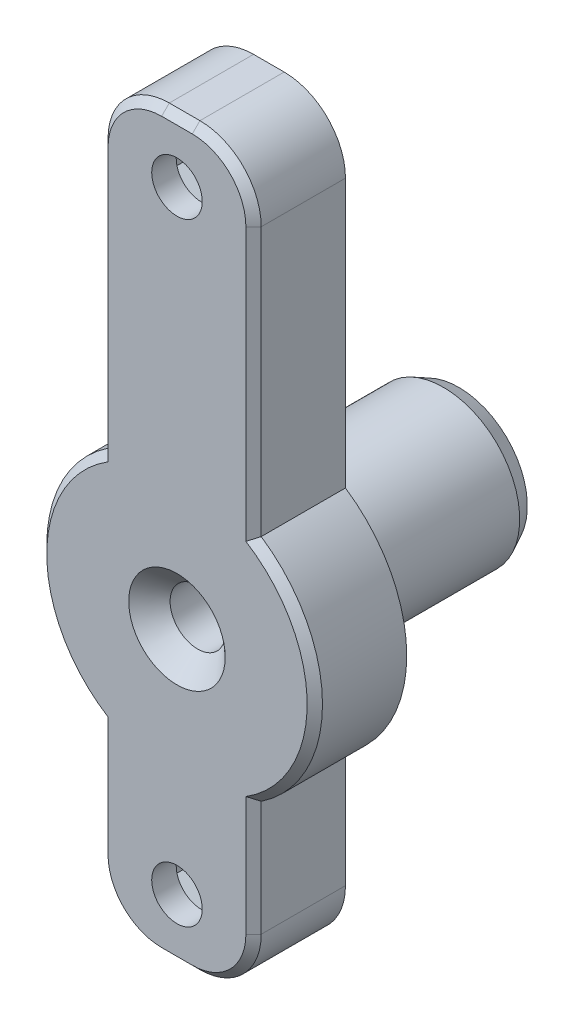
SolidWorks part; units mm, degrees
note: The reader was unsure of these and kept them because the rebuilt part matched: shared geometry of "Sketch1<5>".
material "ABS"
ref_plane "Front Plane" through (0, 0, 0) normal (0, 0, 1) x (1, 0, 0)
ref_plane "Top Plane" through (0, 0, 0) normal (0, 1, 0) x (1, 0, 0)
ref_plane "Right Plane" through (0, 0, 0) normal (1, 0, 0) x (0, 0, -1)
sketch "Sketch1" plane through (0, 0, 0) normal (0, 0, 1) x (1, 0, 0)
  line L0 (-5, 25) -> (-5, 7.4833)
  line L1 (5, 25) -> (5, 7.4833)
  line L2 (-4, 0) -> (-7, 0) construction
  line L3 (-3.9799, 0.4) -> (-6.9886, 0.4)
  line L4 (-3.9799, -0.4) -> (-6.9886, -0.4)
  line L5 (-1.6436, 3.6467) -> (-3.1479, 6.2523)
  line L6 (-4, 0.4) -> (-7, 0.4) construction
  line L7 (-4, -0.4) -> (-7, -0.4) construction
  line L12 (-2.3364, 3.2467) -> (-3.8407, 5.8523)
  line L13 (-2, 3.4641) -> (-3.5, 6.0622) construction
  line L14 (2.3364, 3.2467) -> (3.8407, 5.8523)
  line L15 (1.6436, 3.6467) -> (3.1479, 6.2523)
  line L16 (2, 3.4641) -> (3.5, 6.0622) construction
  line L17 (1, 25) -> (-1, 25) construction
  line L20 (1, 21) -> (-1, 21)
  line L21 (1, 29) -> (-1, 29)
  line L22 (-5, -15) -> (-5, -7.4833)
  line L23 (5, -15) -> (5, -7.4833)
  line L24 (1, -15) -> (-1, -15) construction
  line L25 (1, -19) -> (-1, -19)
  line L26 (1, -11) -> (-1, -11)
  line L27 (-6.5886, 0.4) -> (-7, 0)
  line L28 (-2.9479, 5.9059) -> (-3.5, 6.0622)
  line L29 (3.6407, 5.5059) -> (3.5, 6.0622)
  line L30 (3.9799, -0.4) -> (6.9886, -0.4)
  line L31 (3.9799, 0.4) -> (6.9886, 0.4)
  line L32 (4, 0) -> (7, 0) construction
  line L33 (6.5886, -0.4) -> (7, 0)
  line L34 (1.6436, -3.6467) -> (3.1479, -6.2523)
  line L35 (2.3364, -3.2467) -> (3.8407, -5.8523)
  line L36 (2, -3.4641) -> (3.5, -6.0622) construction
  line L37 (2.9479, -5.9059) -> (3.5, -6.0622)
  line L38 (-2.3364, -3.2467) -> (-3.8407, -5.8523)
  line L39 (-1.6436, -3.6467) -> (-3.1479, -6.2523)
  line L40 (-2, -3.4641) -> (-3.5, -6.0622) construction
  line L41 (-3.6407, -5.5059) -> (-3.5, -6.0622)
  circle A2 centre (0, 0) radius 9
  circle A3 centre (0, 0) radius 7
  circle A4 centre (0, 25) radius 1.65
  circle A5 centre (0, 25) radius 5
  circle A6 centre (0, 0) radius 3.1
  circle A7 centre (0, 0) radius 4
  circle A16 centre (0, 0) radius 1.75
  circle A17 centre (0, 13) radius 1.35 construction
  circle A18 centre (0, -15) radius 1.65
  circle A19 centre (0, -15) radius 5
  arc A20 (1, 21) -> (1, 29) centre (1, 25) ccw
  arc A21 (-1, 29) -> (-1, 21) centre (-1, 25) ccw
  arc A22 (1, -19) -> (1, -11) centre (1, -15) ccw
  arc A23 (-1, -11) -> (-1, -19) centre (-1, -15) ccw
  point P39 (0, 25)
  point P53 (0, -15)
  point P67 (0, 0)
  dimension "D1" = 6.2
  dimension "D2" = 8
  dimension "D3" = 18
  dimension "D4" = 14
  dimension "D5" = 3.3
  dimension "D7" = 10
  dimension "D8" = 0.4
  dimension "D11" = 3.5
  dimension "D12" = 2.7
  dimension "D15" = 3.3
  dimension "D16" = 10
  dimension "D6" = 25
  dimension "D9" = 0.4
  dimension "D10" = 6
  dimension "D13" = 12
  dimension "D14" = 15
  dimension "D17" = 8
  dimension "D18" = 2
  dimension "D19" = 8
  dimension "D20" = 2
  dimension "D21" = 0.4
extrude "Boss-Extrude1" add sketch "Sketch1" along normal blind 6
sketch "Sketch2" plane through (0, 0, 0) normal (0, 0, -1) x (-1, 0, 0)
  line L0 (-0.2571, -2.8886) -> (0, -2.5822)
  line L1 (0, -2.5822) -> (0.2571, -2.8886)
  line L2 (-0.2571, -2.8886) -> (0.2571, -2.8886) construction
  line L3 (-0.9674, -2.7339) -> (-0.6422, -2.501)
  line L4 (-0.6422, -2.501) -> (-0.4693, -2.8618)
  line L5 (-0.9674, -2.7339) -> (-0.4693, -2.8618) construction
  line L6 (-1.6169, -2.4074) -> (-1.244, -2.2628)
  line L7 (-1.244, -2.2628) -> (-1.1663, -2.6551)
  line L8 (-1.6169, -2.4074) -> (-1.1663, -2.6551) construction
  line L9 (-2.1648, -1.9297) -> (-1.7676, -1.8823)
  line L10 (-1.7676, -1.8823) -> (-1.7899, -2.2817)
  line L11 (-2.1648, -1.9297) -> (-1.7899, -2.2817) construction
  line L12 (-2.5767, -1.3307) -> (-2.1802, -1.3836)
  line L13 (-2.1802, -1.3836) -> (-2.3011, -1.7649)
  line L14 (-2.5767, -1.3307) -> (-2.3011, -1.7649) construction
  line L15 (-2.8267, -0.6481) -> (-2.4558, -0.7979)
  line L16 (-2.4558, -0.7979) -> (-2.6677, -1.1372)
  line L17 (-2.8267, -0.6481) -> (-2.6677, -1.1372) construction
  line L18 (-2.899, 0.0752) -> (-2.5771, -0.1621)
  line L19 (-2.5771, -0.1621) -> (-2.8667, -0.438)
  line L20 (-2.899, 0.0752) -> (-2.8667, -0.438) construction
  line L21 (-2.7892, 0.7938) -> (-2.5364, 0.4838)
  line L22 (-2.5364, 0.4838) -> (-2.8856, 0.2887)
  line L23 (-2.7892, 0.7938) -> (-2.8856, 0.2887) construction
  line L24 (-2.5042, 1.4625) -> (-2.3364, 1.0994)
  line L25 (-2.3364, 1.0994) -> (-2.7231, 0.9973)
  line L26 (-2.5042, 1.4625) -> (-2.7231, 0.9973) construction
  line L27 (-2.0618, 2.0394) -> (-1.9896, 1.6459)
  line L28 (-1.9896, 1.6459) -> (-2.3896, 1.6431)
  line L29 (-2.0618, 2.0394) -> (-2.3896, 1.6431) construction
  line L30 (-1.4899, 2.488) -> (-1.5178, 2.089)
  line L31 (-1.5178, 2.089) -> (-1.9059, 2.1858)
  line L32 (-1.4899, 2.488) -> (-1.9059, 2.1858) construction
  line L33 (-0.8243, 2.7804) -> (-0.9506, 2.4008)
  line L34 (-0.9506, 2.4008) -> (-1.3024, 2.5911)
  line L35 (-0.8243, 2.7804) -> (-1.3024, 2.5911) construction
  line L36 (-0.1069, 2.898) -> (-0.3236, 2.5618)
  line L37 (-0.3236, 2.5618) -> (-0.6171, 2.8336)
  line L38 (-0.1069, 2.898) -> (-0.6171, 2.8336) construction
  line L39 (0.6171, 2.8336) -> (0.3236, 2.5618)
  line L40 (0.3236, 2.5618) -> (0.1069, 2.898)
  line L41 (0.6171, 2.8336) -> (0.1069, 2.898) construction
  line L42 (1.3024, 2.5911) -> (0.9506, 2.4008)
  line L43 (0.9506, 2.4008) -> (0.8243, 2.7804)
  line L44 (1.3024, 2.5911) -> (0.8243, 2.7804) construction
  line L45 (1.9059, 2.1858) -> (1.5178, 2.089)
  line L46 (1.5178, 2.089) -> (1.4899, 2.488)
  line L47 (1.9059, 2.1858) -> (1.4899, 2.488) construction
  line L48 (2.3896, 1.6431) -> (1.9896, 1.6459)
  line L49 (1.9896, 1.6459) -> (2.0618, 2.0394)
  line L50 (2.3896, 1.6431) -> (2.0618, 2.0394) construction
  line L51 (2.7231, 0.9973) -> (2.3364, 1.0994)
  line L52 (2.3364, 1.0994) -> (2.5042, 1.4625)
  line L53 (2.7231, 0.9973) -> (2.5042, 1.4625) construction
  line L54 (2.8856, 0.2887) -> (2.5364, 0.4838)
  line L55 (2.5364, 0.4838) -> (2.7892, 0.7938)
  line L56 (2.8856, 0.2887) -> (2.7892, 0.7938) construction
  line L57 (2.8667, -0.438) -> (2.5771, -0.1621)
  line L58 (2.5771, -0.1621) -> (2.899, 0.0752)
  line L59 (2.8667, -0.438) -> (2.899, 0.0752) construction
  line L60 (2.6677, -1.1372) -> (2.4558, -0.7979)
  line L61 (2.4558, -0.7979) -> (2.8267, -0.6481)
  line L62 (2.6677, -1.1372) -> (2.8267, -0.6481) construction
  line L63 (2.3011, -1.7649) -> (2.1802, -1.3836)
  line L64 (2.1802, -1.3836) -> (2.5767, -1.3307)
  line L65 (2.3011, -1.7649) -> (2.5767, -1.3307) construction
  line L66 (1.7899, -2.2817) -> (1.7676, -1.8823)
  line L67 (1.7676, -1.8823) -> (2.1648, -1.9297)
  line L68 (1.7899, -2.2817) -> (2.1648, -1.9297) construction
  line L69 (1.1663, -2.6551) -> (1.244, -2.2628)
  line L70 (1.244, -2.2628) -> (1.6169, -2.4074)
  line L71 (1.1663, -2.6551) -> (1.6169, -2.4074) construction
  line L72 (0.4693, -2.8618) -> (0.6422, -2.501)
  line L73 (0.6422, -2.501) -> (0.9674, -2.7339)
  line L74 (0.4693, -2.8618) -> (0.9674, -2.7339) construction
  circle A0 centre (0, 0) radius 2.9
  point P5 (0, -2.8886)
  point P82 (0, 0)
  dimension "D1" = 5.8
  dimension "D2" = 0.4
  dimension "D3" = 25
  dimension "D4" = 80
  dimension "D5" = 0.5142
extrude "Cut-Extrude3" [suppressed] cut sketch "Sketch2" against normal blind 3.5
hole_wizard "CSK for M3 Countersunk Flat Head Screw1" positions "Sketch3" profile "Sketch4" countersink size "M3" standard "ISO"
sketch "Sketch3" plane through (0, 0, 6) normal (0, 0, 1) x (1, 0, 0)
  point P0 (0, 0)
sketch "Sketch4" plane through (0, 0, 6) normal (1, 0, 0) x (0, -1, 0)
  line L0 (0, 0) -> (0, 48.0815)
  line L1 (0, 48.0815) -> (1.8, 47)
  line L2 (1.8, 47) -> (1.8, 1.35)
  line L3 (1.8, 1.35) -> (3.15, 0)
  line L5 (3.15, 0) -> (0, 0)
  line L6 (-1.8, 1.35) -> (-3.15, 0) construction
  line L10 (0, 48.0815) -> (-1.8, 47) construction
  line L11 (0, -6.35) -> (0, 107.95) construction
  dimension "Hole Dia." = 3.6
  dimension "Hole Depth" = 47
  dimension "Near C'Sink Dia." = 6.3
  dimension "Near C'Sink Angle" = 90
  dimension "Drill Angle" = 118
extrude "Boss-Extrude2" add sketch "Sketch1<5>" along normal blind 6
sketch "Sketch1<5>" plane through (0, 0, 0) normal (0, 0, 1) x (1, 0, 0) same geometry as "Sketch1"
sketch "Sketch5" plane through (0, 0, 0) normal (0, 0, -1) x (-1, 0, 0)
  circle A0 centre (0, 0) radius 6
  dimension "D1" = 12
extrude "Boss-Extrude3" add sketch "Sketch5" along normal blind 1.4
sketch "Sketch6" plane through (0, 0, -1.4) normal (0, 0, -1) x (-1, 0, 0)
  circle A0 centre (0, 0) radius 4.975
  circle M1 centre (0, 0) radius 1.8
  dimension "D1" = 9.95
extrude "Boss-Extrude4" add sketch "Sketch6" along normal blind 11 contours A0 M1
chamfer "Chamfer1" distance 1 distance2 0.5 1 edges at (-4.975, 0, -12.4)
sketch "Sketch7" plane through (0, 0, 0) normal (0, 0, -1) x (-1, 0, 0)
  line L1 (2.85, 23.3546) -> (2.85, 26.6454)
  line L2 (2.85, 26.6454) -> (0, 28.2909)
  line L3 (0, 28.2909) -> (-2.85, 26.6454)
  line L4 (-2.85, 26.6454) -> (-2.85, 23.3546)
  line L5 (-2.85, 23.3546) -> (0, 21.7091)
  line L6 (0, 21.7091) -> (2.85, 23.3546)
  line L7 (2.85, -13.3546) -> (0, -11.7091)
  line L8 (0, -11.7091) -> (-2.85, -13.3546)
  line L9 (-2.85, -13.3546) -> (-2.85, -16.6454)
  line L10 (-2.85, -16.6454) -> (0, -18.2909)
  line L11 (0, -18.2909) -> (2.85, -16.6454)
  line L12 (2.85, -16.6454) -> (2.85, -13.3546)
  circle A0 centre (0, 25) radius 2.85 construction
  circle A1 centre (0, -15) radius 2.85 construction
  circle A2 centre (0, -15) radius 1.65 construction
  dimension "D1" = 5.7
  dimension "D2" = 5.7
extrude "Cut-Extrude4" cut sketch "Sketch7" against normal blind 4.4
chamfer "Chamfer2" distance 0.5 angle 45 12 edges at (-9, 0, 6) (-5, -11.2417, 6) (-5, 16.2417, 6) (-3.8284, -17.8284, 6) (-3.8284, 27.8284, 6) (0, -19, 6) (0, 29, 6) (3.8284, -17.8284, 6) (3.8284, 27.8284, 6) (5, -11.2417, 6) (9, 0, 6) (5, 16.2417, 6)
